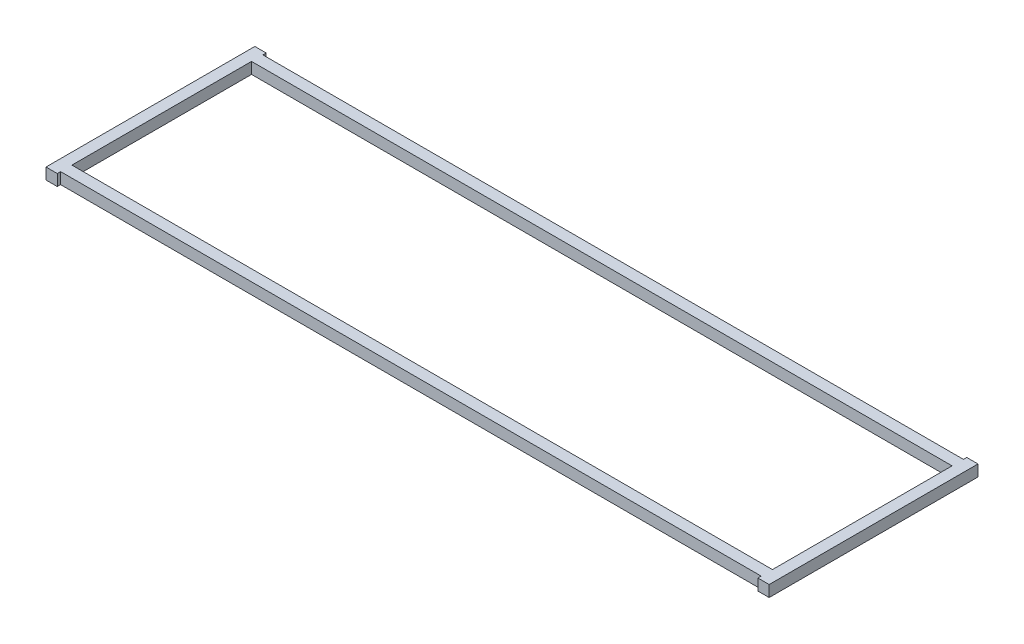
SolidWorks part; units mm, degrees
ref_plane "Front" through (0, 0, 0) normal (0, 0, 1) x (1, 0, 0)
ref_plane "Top" through (0, 0, 0) normal (0, 1, 0) x (1, 0, 0)
ref_plane "Right" through (0, 0, 0) normal (1, 0, 0) x (0, 0, -1)
sketch "Sketch1" plane through (0, 0, 0) normal (0, 1, 0) x (1, 0, 0)
  line L0 (196.85, 58.6835) -> (203.2, 58.6835)
  line L1 (-203.2, 58.6835) -> (-196.85, 58.6835)
  line L2 (-203.2, 58.6835) -> (-203.2, -58.6835)
  line L3 (-203.2, -58.6835) -> (-196.85, -58.6835)
  line L4 (203.2, 58.6835) -> (203.2, -58.6835)
  line L5 (-203.2, 58.6835) -> (203.2, -58.6835) construction
  line L6 (-203.2, -58.6835) -> (203.2, 58.6835) construction
  line L8 (-196.85, 58.6835) -> (-196.85, 56.8196)
  line L9 (-196.85, 56.8196) -> (196.85, 56.8196)
  line L10 (196.85, 58.6835) -> (196.85, 56.8196)
  line L12 (-196.85, -58.6835) -> (-196.85, -56.8196)
  line L13 (-196.85, -56.8196) -> (196.85, -56.8196)
  line L14 (196.85, -58.6835) -> (196.85, -56.8196)
  line L15 (196.85, -58.6835) -> (203.2, -58.6835)
  line L17 (-196.85, -50.4696) -> (196.85, -50.4696)
  line L18 (-196.85, -50.4696) -> (-196.85, 50.4696)
  line L19 (-196.85, 50.4696) -> (196.85, 50.4696)
  line L20 (196.85, -50.4696) -> (196.85, 50.4696)
  line L21 (-196.85, -50.4696) -> (196.85, 50.4696) construction
  line L22 (-196.85, 50.4696) -> (196.85, -50.4696) construction
  point P0 (0, 0)
  point P14 (0, 0)
  dimension "D1" = 406.4
  dimension "D2" = 117.3671
  dimension "D3" = 6.35
  dimension "D4" = 6.35
  dimension "D6" = 6.35
  dimension "D7" = 6.35
  dimension "D5" = 1.8639
extrude "Boss-Extrude1" add sketch "Sketch1" along normal blind 6.35
equation "\"D2@Sketch1\" = (4.87075-.25)"
